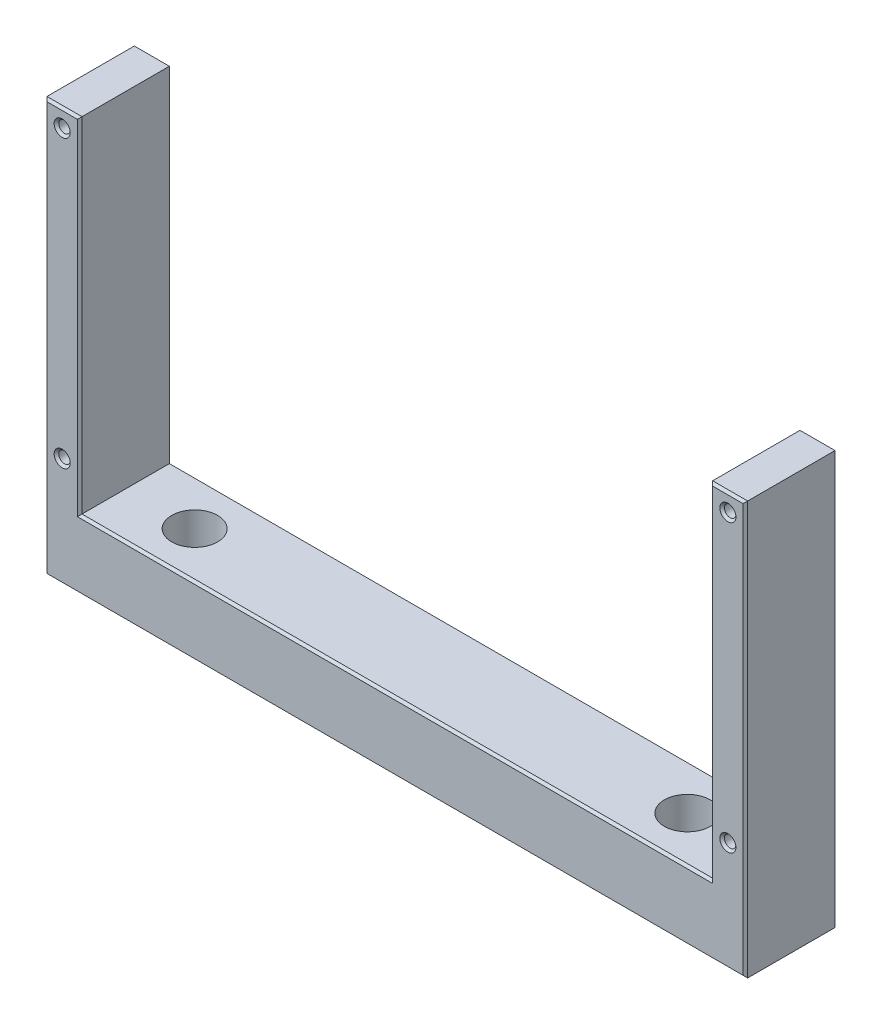
SolidWorks part; units mm, degrees
ref_plane "Front Plane" through (0, 0, 0) normal (0, 0, 1) x (1, 0, 0)
ref_plane "Top Plane" through (0, 0, 0) normal (0, 1, 0) x (1, 0, 0)
ref_plane "Right Plane" through (0, 0, 0) normal (1, 0, 0) x (0, 0, -1)
sketch "Sketch1" plane through (0, 0, 0) normal (0, 0, 1) x (1, 0, 0)
  line L1 (-72.39, 31.115) -> (72.39, 31.115)
  line L2 (-72.39, 31.115) -> (-72.39, -31.115)
  line L3 (-72.39, -31.115) -> (72.39, -31.115)
  line L4 (72.39, 31.115) -> (72.39, -31.115)
  line L5 (-72.39, 31.115) -> (72.39, -31.115) construction
  line L6 (-72.39, -31.115) -> (72.39, 31.115) construction
  line L7 (76.2, 34.925) -> (-76.2, 34.925)
  line L8 (76.2, 34.925) -> (76.2, -34.925)
  line L9 (76.2, -34.925) -> (-76.2, -34.925)
  line L10 (-76.2, 34.925) -> (-76.2, -34.925)
  line L11 (76.2, 34.925) -> (-76.2, -34.925) construction
  line L12 (76.2, -34.925) -> (-76.2, 34.925) construction
  point P0 (0, 0)
  point P6 (0, 0)
  dimension "D1" = 144.78
  dimension "D2" = 62.23
  dimension "D3" = 152.4
  dimension "D4" = 69.85
sketch "Sketch2" plane through (0, 0, 0) normal (0, 0, 1) x (1, 0, 0)
  line L0 (-76.2, 34.925) -> (-68.58, 34.925)
  line L1 (76.2, 34.925) -> (-76.2, 34.925) construction
  line L2 (-68.58, 34.925) -> (-68.58, -39.925)
  line L4 (-68.58, -39.925) -> (68.58, -39.925)
  line L5 (68.58, -39.925) -> (68.58, 34.925)
  line L6 (68.58, 34.925) -> (76.2, 34.925)
  line L7 (76.2, 34.925) -> (76.2, -54.925)
  line L8 (76.2, -54.925) -> (-76.2, -54.925)
  line L9 (-76.2, -54.925) -> (-76.2, 34.925)
  line L10 (-72.39, 31.115) -> (-72.39, 34.925) construction
  line L11 (76.2, -34.925) -> (-76.2, -34.925) construction
  point P7 (-68.58, -43.3507)
  dimension "D1" = 15
  dimension "D2" = 5
extrude "Boss-Extrude1" add sketch "Sketch2" along normal blind 20
hole_wizard "M3x0.5 Tapped Hole1" positions "Sketch3" profile "Sketch4" tap size "M3x0.5" standard "ANSI Metric" end condition through all
sketch "Sketch3" plane through (0, 0, 0) normal (0, 0, -1) x (-1, 0, 0)
  point P0 (-72.39, -31.115)
  point P3 (-72.39, 31.115)
  point P6 (72.39, 31.115)
  point P9 (72.39, -31.115)
sketch "Sketch4" plane through (72.39, -31.115, 0) normal (1, 0, 0) x (0, 1, 0)
  line L0 (0, 0) -> (0, 20)
  line L1 (0, 20) -> (1.25, 20)
  line L2 (1.25, 20) -> (1.25, 0)
  line L5 (1.25, 0) -> (0, 0)
  line L11 (0, -6.35) -> (0, 107.95) construction
  dimension "Thru Tap Drill Dia." = 2.5
  dimension "Thru Tap Drill Depth" = 20
cosmetic thread "Hole Thread1" parameters "D2"=3
cosmetic thread "Hole Thread2" parameters "D2"=3
cosmetic thread "Hole Thread3" parameters "D2"=3
cosmetic thread "Hole Thread4" parameters "D2"=3
chamfer "Chamfer1" distance 0.5 angle 45 24 edges at (0, -54.925, 0) (68.58, -2.5, 0) (0, -39.925, 0) (-68.58, -2.5, 0) (-72.39, 34.925, 0) (-76.2, -10, 0) (-73.64, -31.115, 0) (-73.64, 31.115, 0) (71.14, 31.115, 0) (71.14, -31.115, 0) (-72.39, 34.925, 20) (-68.58, -2.5, 20) (0, -39.925, 20) (72.39, 34.925, 20) (0, -54.925, 20) (-76.2, -10, 20) (-73.64, -31.115, 20) (-73.64, 31.115, 20) (71.14, 31.115, 20) (71.14, -31.115, 20) (68.58, -2.5, 20) (72.39, 34.925, 0) (76.2, -10, 20) (76.2, -10, 0)
hole_wizard "CBORE for M5 SHCS1" positions "3DSketch1" profile "Sketch6" counterbore size "M5" standard "ANSI Metric" end condition through all
sketch3d "3DSketch1"
  line L0 (-68.58, -39.925, 10) -> (68.58, -39.925, 10)
  line L1 (-68.58, -39.925, 19.5) -> (-68.58, -39.925, 0.5) construction
  line L2 (68.58, -39.925, 19.5) -> (68.58, -39.925, 0.5) construction
  point P1 (-53.58, -39.925, 10)
  point P3 (53.58, -39.925, 10)
  point P13 (0, 0, 0)
  point P14 (0, 0, 0)
  dimension "D1" = 15
  dimension "D2" = 15
sketch "Sketch6" plane through (-53.58, -39.925, 10) normal (1, 0, 0) x (0, 0, 1)
  line L0 (0, 0) -> (0, 15)
  line L1 (0, 15) -> (2.75, 15)
  line L3 (2.75, 15) -> (2.75, 10)
  line L4 (2.75, 10) -> (5, 10)
  line L5 (5, 10) -> (5, 0)
  line L7 (5, 0) -> (0, 0)
  line L11 (0, -6.35) -> (0, 107.95) construction
  dimension "Thru Hole Dia." = 5.5
  dimension "Thru Hole Depth" = 15
  dimension "C'Bore Dia." = 10
  dimension "C'Bore Depth" = 10
